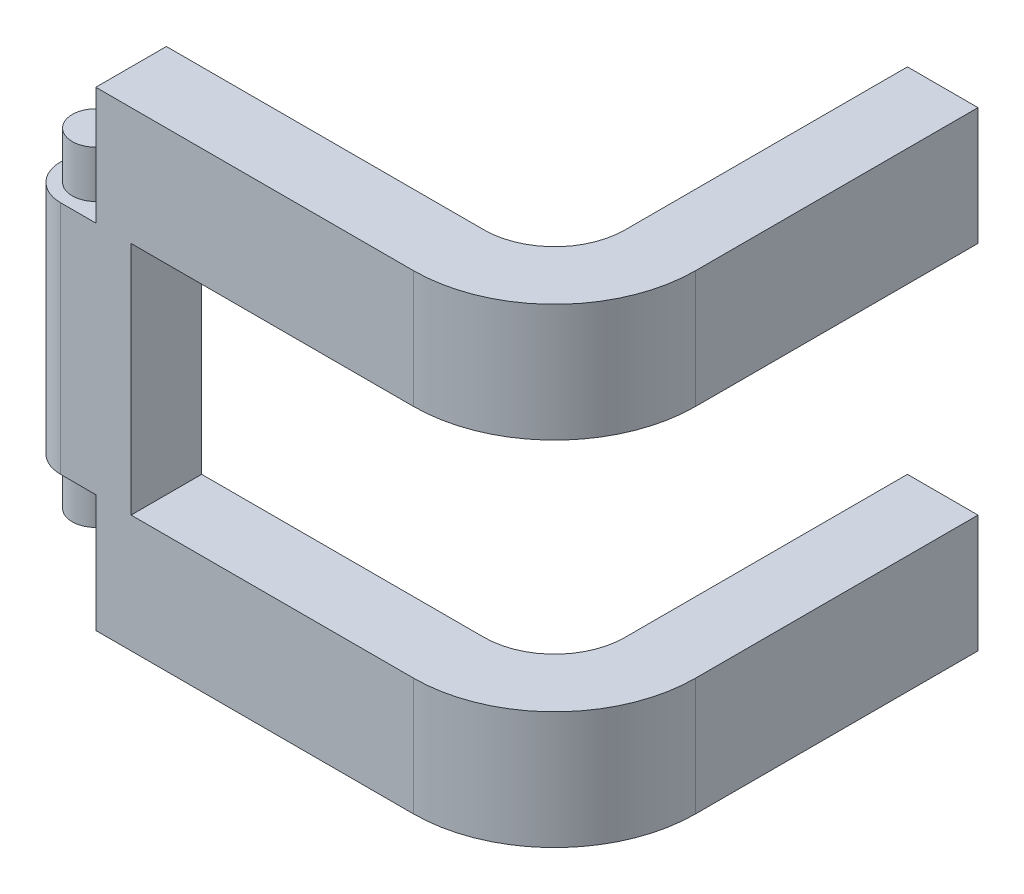
SolidWorks part; units mm, degrees
ref_plane "前视基准面" through (0, 0, 0) normal (0, 0, 1) x (1, 0, 0)
ref_plane "上视基准面" through (0, 0, 0) normal (0, 1, 0) x (1, 0, 0)
ref_plane "右视基准面" through (0, 0, 0) normal (1, 0, 0) x (0, 0, -1)
sketch "草图1" plane through (0, 0, 0) normal (0, 1, 0) x (1, 0, 0)
  line L0 (0, 7.5) -> (75, 7.5)
  line L1 (0, -7.5) -> (75, -7.5)
  line L2 (90, 22.5) -> (90, 82.5)
  line L3 (105, 22.5) -> (105, 82.5)
  line L4 (90, 82.5) -> (105, 82.5)
  arc A0 (0, 7.5) -> (0, -7.5) centre (0, 0) ccw
  arc A1 (75, 7.5) -> (90, 22.5) centre (75, 22.5) ccw
  arc A2 (75, -7.5) -> (105, 22.5) centre (75, 22.5) ccw
extrude "凸台-拉伸1" add sketch "草图1" along normal mid plane 100
ref_plane "基准面4" through (0, 25, 0) normal (0, 1, 0) x (1, 0, 0)
ref_plane "基准面5" through (0, -25, 0) normal (0, 1, 0) x (1, 0, 0)
ref_plane "基准面6" through (0, 0, 0) normal (1, 0, 0) x (0, 0, -1)
ref_plane "基准面7" through (15, 0, 0) normal (1, 0, 0) x (0, 0, -1)
sketch "草图2" plane through (0, 25, 0) normal (0, 1, 0) x (1, 0, 0)
  line L0 (15, -8.25) -> (15, 8.25) construction
  line L1 (15, -10.9241) -> (114.7859, -10.9241)
  line L2 (15, -10.9241) -> (15, 89.0759)
  line L3 (15, 89.0759) -> (114.7859, 89.0759)
  line L4 (114.7859, -10.9241) -> (114.7859, 89.0759)
extrude "切除-拉伸1" cut sketch "草图2" against normal up to surface (50 mm away) up to plane "基准面5"
ref_plane "基准面8" through (7.5, 0, 0) normal (1, 0, 0) x (0, 0, -1)
ref_axis "基准轴4" through (7.5, 50, -8.25) along (0, 0, 1)
sketch "草图7" plane through (0, 50, 0) normal (0, 1, 0) x (1, 0, 0)
  line L0 (7.5, 7.5) -> (7.5, -7.5)
  line L1 (75, 7.5) -> (0, 7.5) construction
  line L2 (0, -7.5) -> (75, -7.5) construction
  line L3 (7.5, -7.5) -> (-11.5444, -7.5)
  line L4 (-11.5444, -7.5) -> (-11.5444, 7.5)
  line L5 (-11.5444, 7.5) -> (7.5, 7.5)
  line L7 (7.5, 8.25) -> (7.5, -8.25) construction
extrude "切除-拉伸5" cut sketch "草图7" against normal blind 15 contours L4 L5 L0 L3
mirror "镜向1" about plane through (0, 0, 0) normal (0, 1, 0) of "切除-拉伸5"
sketch "草图9" plane through (0, 35, 0) normal (0, 1, 0) x (1, 0, 0)
  line L0 (0, 7.5) -> (7.5, 7.5)
  line L1 (7.5, -8.25) -> (7.5, 8.25) construction
  line L2 (7.5, 7.5) -> (7.5, -7.5)
  line L3 (7.5, -7.5) -> (0, -7.5) construction
  line L4 (7.5, -7.5) -> (0, -7.5)
  circle A0 centre (0, 0) radius 5
  arc A1 (0, 7.5) -> (0, -7.5) centre (0, 0) ccw
extrude "切除-拉伸6" cut sketch "草图9" against normal blind 10
mirror "镜向2" about plane through (0, 0, 0) normal (0, 1, 0) of "切除-拉伸6"
